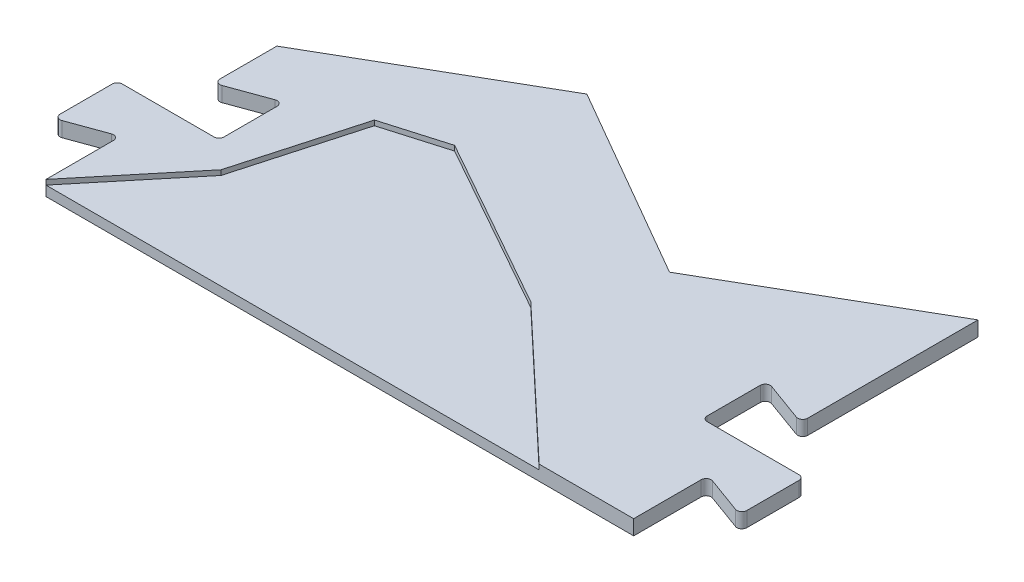
SolidWorks part; units mm, degrees
ref_plane "Přední rovina" through (0, 0, 0) normal (0, 0, 1) x (1, 0, 0)
ref_plane "Horní rovina" through (0, 0, 0) normal (0, 1, 0) x (1, 0, 0)
ref_plane "Pravá rovina" through (0, 0, 0) normal (1, 0, 0) x (0, 0, -1)
sketch "Skica1" plane through (0, 0, 0) normal (0, 1, 0) x (1, 0, 0)
  line L0 (-118.1438, 0) -> (-118.1438, 15)
  line L1 (-118.1438, 15) -> (-128.0938, 11.3785)
  line L2 (-128.0938, 11.3785) -> (-128.0938, 24.2785)
  line L3 (-107.6438, 24.2785) -> (-107.6438, 37.3785)
  line L4 (-107.6438, 37.3785) -> (-118.1432, 33.557)
  line L5 (-118.1432, 33.557) -> (-118.1432, 46.4149)
  line L6 (-118.1432, 46.4149) -> (-78.6351, 69.2249)
  line L7 (-78.6351, 69.2249) -> (-39.3176, 46.5249)
  line L8 (-118.1438, 15) -> (-118.1438, 58.9257) construction
  line L9 (-107.6438, 24.2785) -> (-128.0938, 24.2785)
  line L10 (-118.1438, 0) -> (-102.2271, 19.2785)
  line L11 (-102.2271, 19.2785) -> (-95.473, 43.3489)
  line L12 (-95.473, 43.3489) -> (-82.9972, 47.0032)
  line L13 (-82.9972, 47.0032) -> (-48.113, 27.4305)
  line L14 (-39.3176, 46.5249) -> (0, 69.2249)
  line L15 (-118.1438, 0) -> (0, 0)
  line L16 (-48.113, 27.4305) -> (-19, 0)
  line L17 (0, 0) -> (0, 15)
  line L18 (0, 69.2249) -> (0, 0) construction
  line L19 (-10.5, 24.2783) -> (9.9505, 24.2783)
  line L20 (0, 69.2249) -> (0, 33.5566)
  line L21 (0, 15) -> (9.9505, 11.3783)
  line L22 (9.9505, 24.2783) -> (9.9505, 11.3783)
  line L23 (0, 33.5566) -> (-10.5, 37.3783)
  line L24 (-10.5, 37.3783) -> (-10.5, 24.2783)
  point P23 (-0.2747, 24.2783)
  dimension "D1" = 45.4
  dimension "D2" = 45.62
  dimension "D3" = 120
  dimension "D4" = 70
  dimension "D5" = 12.9
  dimension "D6" = 13.1
  dimension "D7" = 15
  dimension "D8" = 69.2249
  dimension "D9" = 69.2249
  dimension "D10" = 25
  dimension "D11" = 25
  dimension "D12" = 13
  dimension "D13" = 40
  dimension "D14" = 45.4
  dimension "D15" = 120
  dimension "D16" = 118.1438
  dimension "D17" = 40
  dimension "D18" = 122
  dimension "D19" = 15
  dimension "D20" = 70
  dimension "D21" = 70
  dimension "D22" = 5
  dimension "D23" = 120
  dimension "D24" = 19
  dimension "D25" = 166
  dimension "D26" = 10.5
  dimension "D27" = 12.9
  dimension "D28" = 13.1
  dimension "D29" = 10.5
  dimension "D30" = 70
  dimension "D31" = 9.95
extrude "Přidat vysunutím1" add sketch "Skica1" along normal blind 3 contours L24 L23 L20 L14 L7 L6 L5 L4 L3 L9 L2 L1 L0 L10 L11 L12 L13 L16 L15 L17 L21 L22 L19 region at (-50.0339, 0, -36.1877)
extrude "Přidat vysunutím2" add sketch "Skica1<3>" along normal blind 2 contours L16 L13 L12 L11 L10 L15 region at (-72.3465, 0, -17.3507)
sketch "Skica1<3>" plane through (0, 0, 0) normal (0, 1, 0) x (1, 0, 0) same geometry as "Skica1"
fillet "Zaoblit3" radius 1 12 edges at (-107.6438, 1.5, -24.2785) (0, 1.5, -15) (9.9505, 1.5, -11.3783) (9.9505, 1.5, -24.2783) (-10.5, 1.5, -24.2783) (-10.5, 1.5, -37.3783) (0, 1.5, -33.5566) (-118.1438, 1.5, -15) (-128.0938, 1.5, -11.3785) (-128.0938, 1.5, -24.2785) (-107.6438, 1.5, -37.3785) (-118.1432, 1.5, -33.557)
